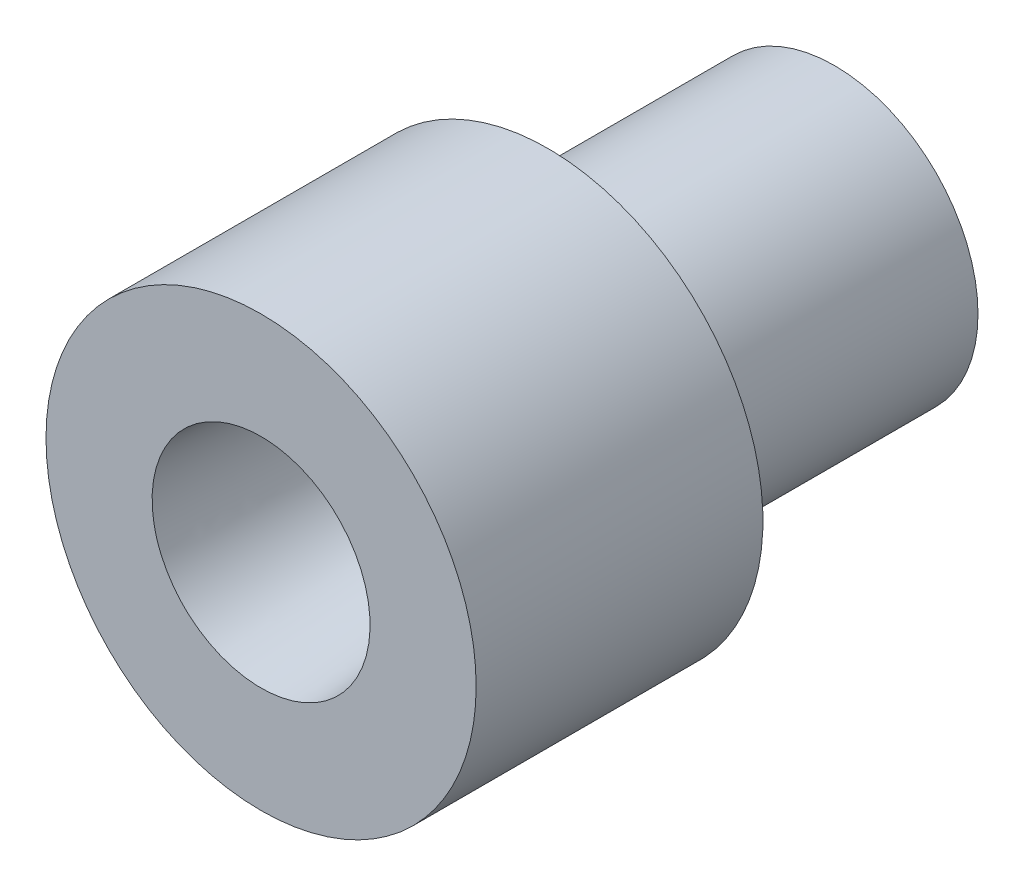
SolidWorks part; units mm, degrees
material "6061 Alloy"
ref_plane "Front Plane" through (0, 0, 0) normal (0, 0, 1) x (1, 0, 0)
ref_plane "Top Plane" through (0, 0, 0) normal (0, 1, 0) x (1, 0, 0)
ref_plane "Right Plane" through (0, 0, 0) normal (1, 0, 0) x (0, 0, -1)
sketch "Sketch1" plane through (0, 0, 0) normal (0, 0, 1) x (1, 0, 0)
  circle A0 centre (0, 0) radius 9.525
extrude "Boss-Extrude1" add sketch "Sketch1" along normal blind 25.4
sketch "Sketch2" plane through (0, 0, 0) normal (0, 0, -1) x (-1, 0, 0)
  circle A0 centre (0, 0) radius 2.3813
sketch "Sketch3" plane through (0, 0, 25.4) normal (0, 0, 1) x (1, 0, 0)
  circle A0 centre (0, 0) radius 4.826
loft "Cut-Loft1" cut profiles "Sketch3", "Sketch2" connector at (4.189, 2.3963, 25.4) connector at (2.246, 0.7911, 0)
sketch "Sketch4" plane through (0, 0, 0) normal (0, 0, -1) x (-1, 0, 0)
  circle A0 centre (0, 0) radius 6.35
  circle A1 centre (0, 0) radius 9.525
extrude "Cut-Extrude1" cut sketch "Sketch4" against normal blind 12.7
